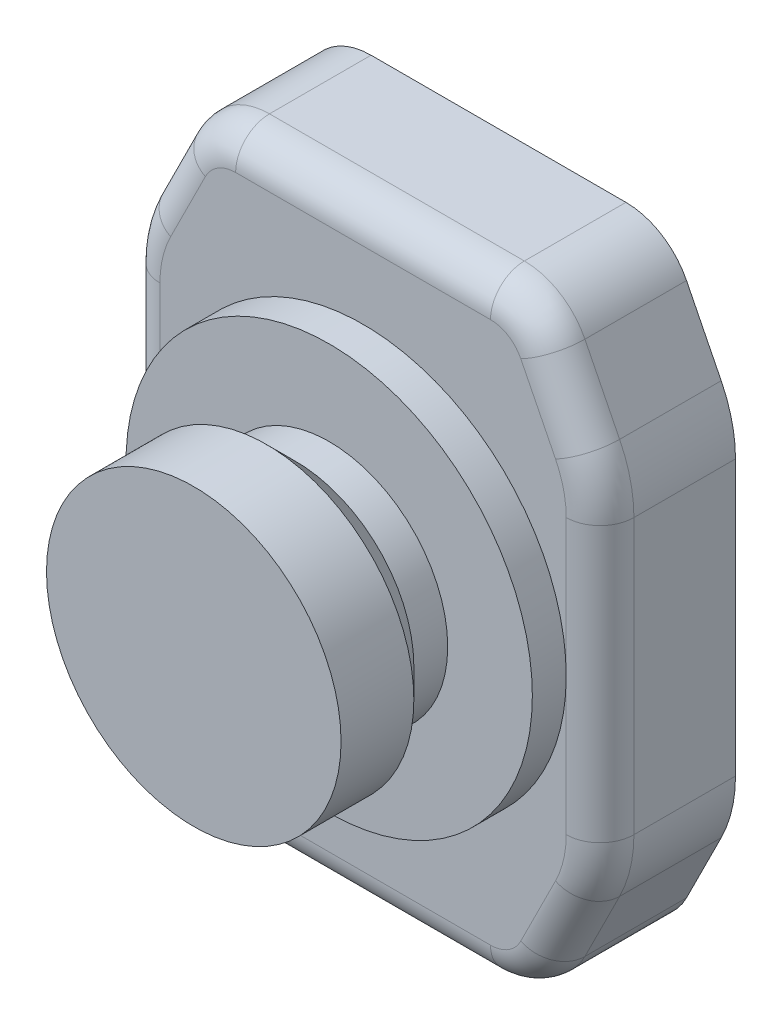
SolidWorks part; units mm, degrees
ref_plane "Front Plane" through (0, 0, 0) normal (0, 0, 1) x (1, 0, 0)
ref_plane "Top Plane" through (0, 0, 0) normal (0, 1, 0) x (1, 0, 0)
ref_plane "Right Plane" through (0, 0, 0) normal (1, 0, 0) x (0, 0, -1)
sketch "Sketch1" plane through (0, 0, 0) normal (0, 0, 1) x (1, 0, 0)
  line L0 (-32.8885, 29.2229) -> (-27.7639, 39.4721)
  line L1 (-18.8197, -45) -> (18.8197, -45)
  line L2 (-35, -20.2786) -> (-35, 20.2786)
  line L3 (-18.8197, 45) -> (18.8197, 45)
  line L4 (35, -20.2786) -> (35, 20.2786)
  line L5 (-35, -45) -> (35, 45) construction
  line L6 (-35, 45) -> (35, -45) construction
  line L7 (27.7639, 39.4721) -> (32.8885, 29.2229)
  line L8 (-32.8885, -29.2229) -> (-27.7639, -39.4721)
  line L9 (27.7639, -39.4721) -> (32.8885, -29.2229)
  arc A0 (-27.7639, -39.4721) -> (-18.8197, -45) centre (-18.8197, -35) ccw
  arc A1 (27.7639, -39.4721) -> (18.8197, -45) centre (18.8197, -35) cw
  arc A2 (27.7639, 39.4721) -> (18.8197, 45) centre (18.8197, 35) ccw
  arc A3 (-27.7639, 39.4721) -> (-18.8197, 45) centre (-18.8197, 35) cw
  arc A4 (32.8885, 29.2229) -> (35, 20.2786) centre (15, 20.2786) cw
  arc A5 (32.8885, -29.2229) -> (35, -20.2786) centre (15, -20.2786) ccw
  arc A6 (-32.8885, -29.2229) -> (-35, -20.2786) centre (-15, -20.2786) cw
  arc A7 (-32.8885, 29.2229) -> (-35, 20.2786) centre (-15, 20.2786) ccw
  point P0 (0, 0)
  point P16 (-25, -45)
  point P19 (25, -45)
  point P22 (25, 45)
  point P25 (-25, 45)
  point P28 (35, 25)
  point P31 (35, -25)
  point P34 (-35, -25)
  point P37 (-35, 25)
  point P38 (0, 0)
  dimension "D11" = 10
  dimension "D12" = 20
  dimension "D1" = 70
  dimension "D2" = 90
  dimension "D3" = 20
  dimension "D4" = 10
  dimension "D5" = 10
  dimension "D6" = 20
  dimension "D7" = 10
  dimension "D8" = 20
  dimension "D9" = 10
  dimension "D10" = 20
extrude "Boss-Extrude1" add sketch "Sketch1" along normal blind 20
fillet "Fillet1" radius 5 16 edges at (-30.3262, -34.3475, 20) (-34.465, -24.8737, 20) (-35, 0, 20) (-34.465, 24.8737, 20) (-30.3262, 34.3475, 20) (-24.077, 43.5065, 20) (0, 45, 20) (24.077, 43.5065, 20) (30.3262, 34.3475, 20) (34.465, 24.8737, 20) (35, 0, 20) (34.465, -24.8737, 20) (30.3262, -34.3475, 20) (24.077, -43.5065, 20) (0, -45, 20) (-24.077, -43.5065, 20)
sketch "Sketch2" plane through (0, 0, 20) normal (0, 0, 1) x (1, 0, 0)
  circle A0 centre (0, 0) radius 30
  dimension "D1" = 60
extrude "Boss-Extrude2" add sketch "Sketch2" along normal blind 5
sketch "Sketch3" plane through (0, 0, 25) normal (0, 0, 1) x (1, 0, 0)
  circle A0 centre (0, 0) radius 17.5
  dimension "D1" = 35
extrude "Boss-Extrude3" add sketch "Sketch3" along normal blind 10
sketch "Sketch4" plane through (0, 0, 35) normal (0, 0, 1) x (1, 0, 0)
  circle A0 centre (0, 0) radius 21.75
  dimension "D1" = 43.5
extrude "Boss-Extrude4" add sketch "Sketch4" along normal blind 10
chamfer "Chamfer1" distance 5 angle 45 1 edges at (17.5, 0, 35)
